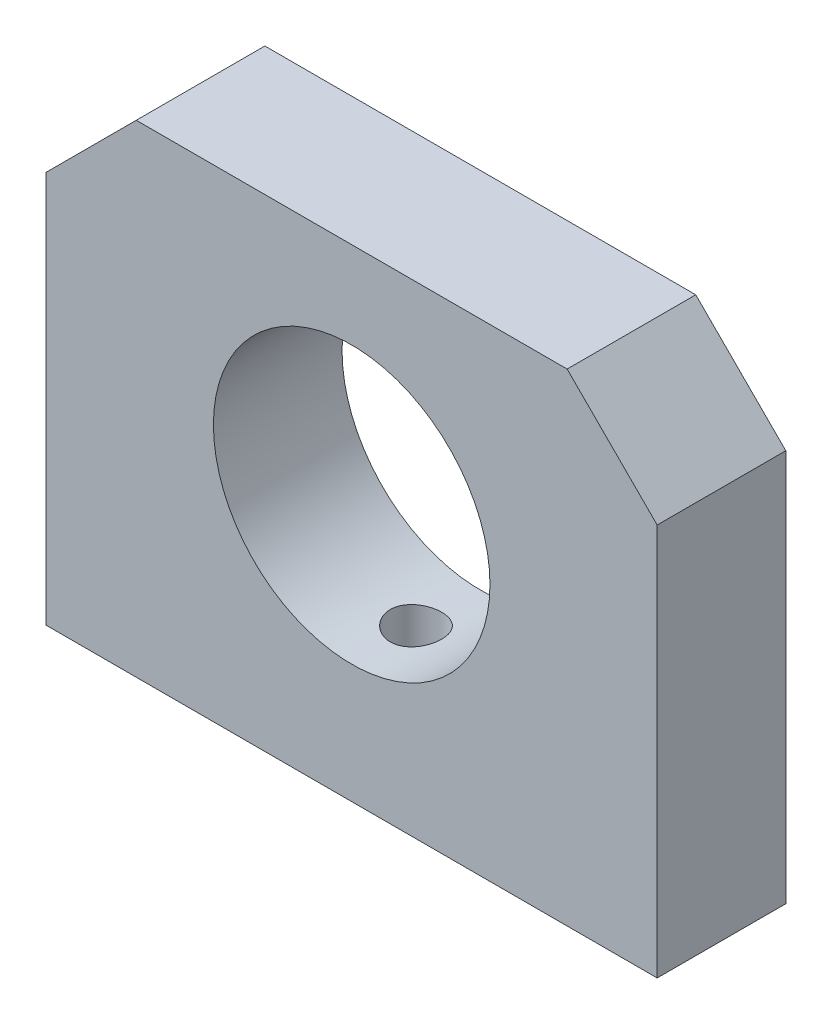
SolidWorks part; units mm, degrees
ref_plane "Piano frontale" through (0, 0, 0) normal (0, 0, 1) x (1, 0, 0)
ref_plane "Piano superiore" through (0, 0, 0) normal (0, 1, 0) x (1, 0, 0)
ref_plane "Piano destro" through (0, 0, 0) normal (1, 0, 0) x (0, 0, -1)
sketch "Schizzo1" plane through (0, 0, 0) normal (0, 0, 1) x (1, 0, 0)
  line L0 (47.5, 75) -> (47.5, 0) construction
  line L1 (0, 0) -> (95, 0)
  line L2 (0, 0) -> (0, 61)
  line L3 (14, 75) -> (81, 75)
  line L4 (95, 0) -> (95, 61)
  line L5 (0, 37.5) -> (95, 37.5) construction
  line L6 (0, 61) -> (14, 75)
  line L7 (81, 75) -> (95, 61)
  circle A0 centre (47.5, 40) radius 21.5
  point P1 (95, 75)
  point P2 (0, 75)
  dimension "D4" = 43
  dimension "D1" = 75
  dimension "D2" = 95
  dimension "D3" = 40
extrude "Estrusione-Estrusione1" add sketch "Schizzo1" along normal blind 20
sketch "Schizzo2" plane through (0, 0, 0) normal (0, -1, 0) x (1, 0, 0)
  line L0 (0, 10) -> (95, 10) construction
  line L1 (0, 20) -> (0, 0) construction
  line L2 (95, 20) -> (95, 0) construction
  line L3 (47.5, 20) -> (47.5, 0) construction
  line L4 (0, 20) -> (95, 20) construction
  line L5 (0, 0) -> (95, 0) construction
  circle A0 centre (47.5, 10) radius 4
  circle A1 centre (15.8899, 10) radius 4
  circle A2 centre (79.1101, 10) radius 4
  dimension "D1" = 8
extrude "Taglio-Estrusione1" cut sketch "Schizzo2" against normal blind 20
